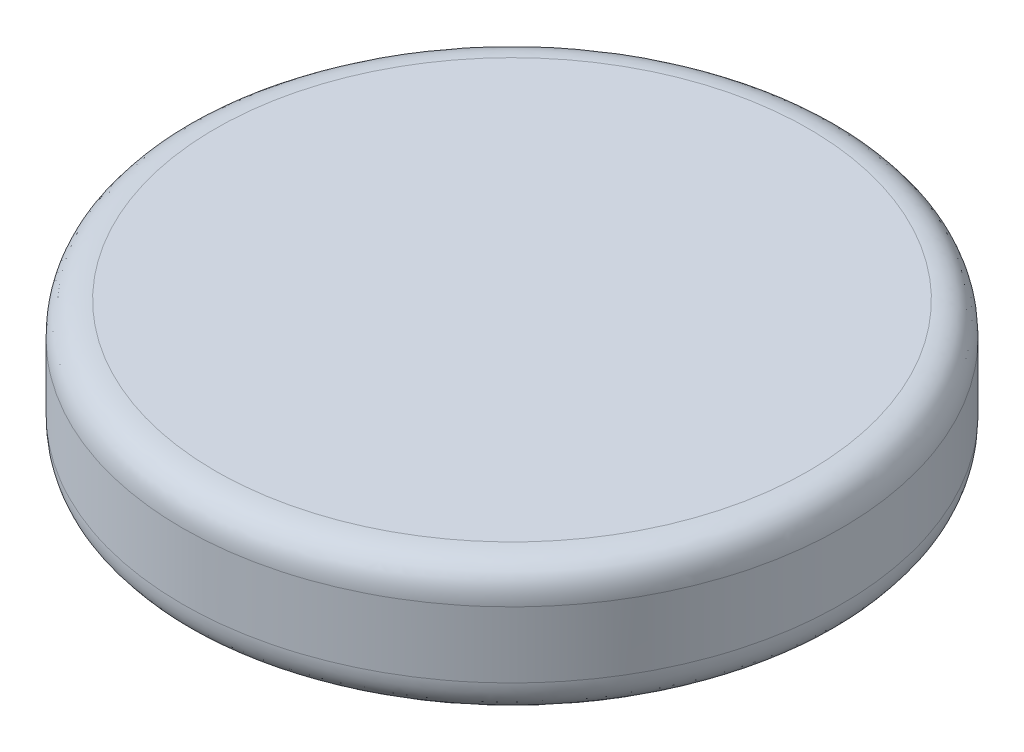
SolidWorks part; units mm, degrees
ref_plane "Front Plane" through (0, 0, 0) normal (0, 0, 1) x (1, 0, 0)
ref_plane "Top Plane" through (0, 0, 0) normal (0, 1, 0) x (1, 0, 0)
ref_plane "Right Plane" through (0, 0, 0) normal (1, 0, 0) x (0, 0, -1)
sketch "Sketch1" plane through (0, 0, 0) normal (0, 1, 0) x (1, 0, 0)
  circle A0 centre (0, 0) radius 100
  dimension "D1" = 200
extrude "Boss-Extrude1" add sketch "Sketch1" along normal blind 40
sketch "Sketch2" plane through (0, 0, 0) normal (0, -1, 0) x (1, 0, 0)
  circle A0 centre (0, 0) radius 15
extrude "Cut-Extrude1" cut sketch "Sketch2" against normal blind 7
fillet "Fillet2" radius 10 2 edges at (0, 40, 100) (0, 0, 100) conic rho 0.5
